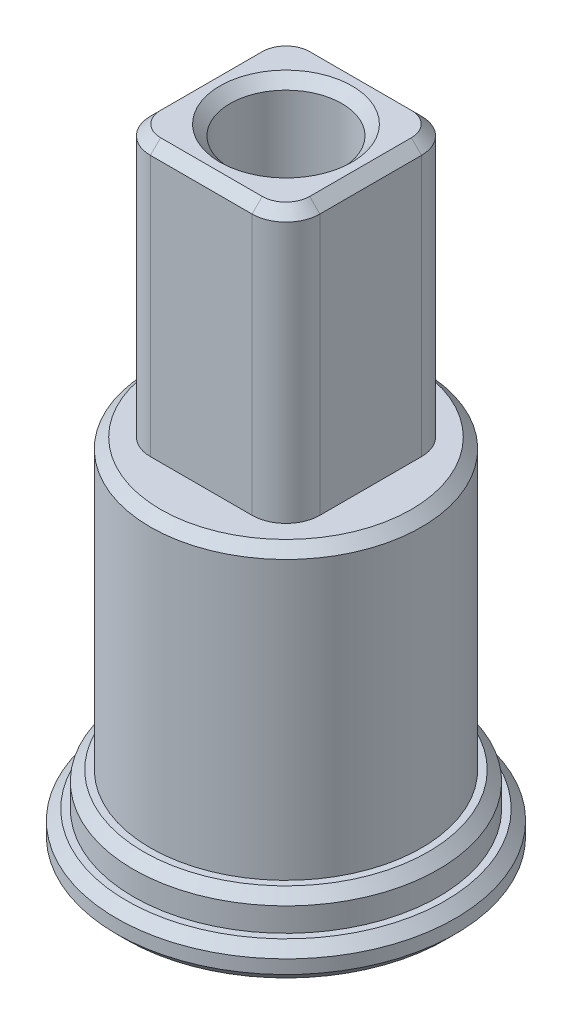
SolidWorks part; units mm, degrees
material "보통 탄소강"
ref_plane "정면" through (0, 0, 0) normal (0, 0, 1) x (1, 0, 0)
ref_plane "윗면" through (0, 0, 0) normal (0, 1, 0) x (1, 0, 0)
ref_plane "우측면" through (0, 0, 0) normal (1, 0, 0) x (0, 0, -1)
sketch "스케치1" plane through (0, 0, 0) normal (0, 1, 0) x (1, 0, 0)
  line L1 (2.5, -2.5) -> (-2.5, -2.5)
  line L2 (2.5, -2.5) -> (2.5, 2.5)
  line L3 (2.5, 2.5) -> (-2.5, 2.5)
  line L4 (-2.5, -2.5) -> (-2.5, 2.5)
  line L5 (2.5, -2.5) -> (-2.5, 2.5) construction
  line L6 (2.5, 2.5) -> (-2.5, -2.5) construction
  circle A0 centre (0, 0) radius 4
  circle A1 centre (0, 0) radius 5
  circle A2 centre (0, 0) radius 4.5
  dimension "D1" = 8
  dimension "D2" = 10
  dimension "D3" = 9
  dimension "D4" = 5
extrude "보스-돌출1" add sketch "스케치1" along normal blind 1 contours A1 A2 region at (-4.8586, 0, 0)
extrude "보스-돌출2" add sketch "스케치1<5>" along normal blind 2 contours A2 A0 region at (-4.3727, 0, 0)
sketch "스케치1<5>" plane through (0, 0, 0) normal (0, 1, 0) x (1, 0, 0) same geometry as "스케치1"
extrude "보스-돌출3" add sketch "스케치1<6>" along normal blind 10.5 contours A0 L1 L4 L3 L2 | L4 L1 L2 L3 region at (0, 0, 0) region at (-3.8869, 0, 0)
sketch "스케치1<6>" plane through (0, 0, 0) normal (0, 1, 0) x (1, 0, 0) same geometry as "스케치1"
extrude "보스-돌출4" add sketch "스케치1<7>" along normal blind 18.5 contours L4 L1 L2 L3 region at (0, 0, 0)
sketch "스케치1<7>" plane through (0, 0, 0) normal (0, 1, 0) x (1, 0, 0) same geometry as "스케치1"
sketch "스케치3" plane through (0, 0, 0) normal (0, -1, 0) x (1, 0, 0)
  line L0 (0, 1) -> (0, -1) construction
  line L1 (1, 1) -> (1, -1)
  line L2 (-1, 1) -> (-1, -1)
  arc A0 (1, 1) -> (-1, 1) centre (0, 1) ccw
  arc A1 (-1, -1) -> (1, -1) centre (0, -1) ccw
  point P3 (0, 0)
  dimension "D1" = 1
  dimension "D2" = 2
extrude "컷-돌출1" cut sketch "스케치3" against normal blind 1
sketch "스케치5" plane through (0, 18.5, 0) normal (0, 1, 0) x (1, 0, 0)
  circle A0 centre (0, 0) radius 1.65
  dimension "D1" = 3.3
sketch "스케치4" plane through (0, 0, 0) normal (0, 0, 1) x (1, 0, 0)
  line L0 (0, -0.5862) -> (0, 5.0613) construction
  line L1 (0, 8.5) -> (-1.65, 8.5)
  line L3 (-1.65, 8.5) -> (0, 7.8165)
  line L4 (0, 8.5) -> (0, 7.8165)
  line L5 (2.5, 18.5) -> (-2.5, 18.5) construction
  dimension "D1" = 67.5
  dimension "D2" = 1.65
  dimension "D3" = 10
revolve "컷-회전1" cut sketch "스케치4" angle 360 about L0
extrude "컷-돌출2" cut sketch "스케치5" against normal blind 10
fillet "필렛1" radius 1 4 edges at (2.5, 14.5, 2.5) (2.5, 14.5, -2.5) (-2.5, 14.5, 2.5) (-2.5, 14.5, -2.5)
chamfer "모따기1" distance 0.3 angle 45 13 edges at (0, 18.5, 1.65) (0, 0, 5) (0, 1, 5) (0, 2, 4.5) (0, 10.5, 4) (2.5, 18.5, 0) (0, 18.5, -2.5) (-2.5, 18.5, 0) (0, 18.5, 2.5) (2.2071, 18.5, 2.2071) (-2.2071, 18.5, 2.2071) (2.2071, 18.5, -2.2071) (-2.2071, 18.5, -2.2071)
